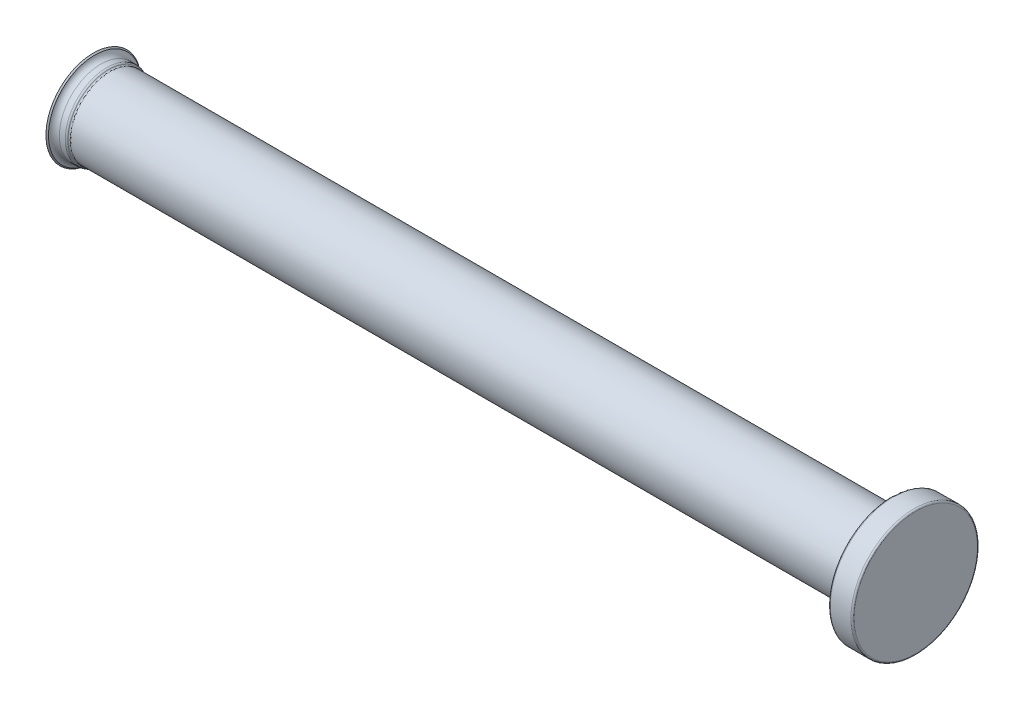
SolidWorks part; units mm, degrees
ref_plane "Ön Düzlem" through (0, 0, 0) normal (0, 0, 1) x (1, 0, 0)
ref_plane "Üst Düzlem" through (0, 0, 0) normal (0, 1, 0) x (1, 0, 0)
ref_plane "Sağ Düzlem" through (0, 0, 0) normal (1, 0, 0) x (0, 0, -1)
sketch "Çizim1" plane through (0, 0, 0) normal (0, 0, 1) x (1, 0, 0)
  line L0 (0, 0) -> (-51, 0)
  line L1 (0, 0) -> (0, 4)
  line L2 (0, 4) -> (-1.5, 4)
  line L3 (-1.5, 4) -> (-1.5, 2.5)
  line L4 (-1.5, 2.5) -> (-51, 2.5)
  line L5 (0, 0) -> (21.8777, 0) construction
  line L6 (-51, 2.5) -> (-51, 0)
  dimension "D1" = 5
  dimension "D2" = 1.5
  dimension "D3" = 8
  dimension "D4" = 49.5
revolve "Döndür1" add sketch "Çizim1" angle 360 about L5
fillet "Radyus1" radius 0.1 2 edges at (0, 0, 4) (-1.5, 0, 4)
sketch "Çizim3" plane through (-51, 0, 0) normal (-1, 0, 0) x (0, 0, 1)
  circle A1 centre (0, 0) radius 2.5
  circle A2 centre (0, 0) radius 2.5
  dimension "D1" = 0
extrude "Kes-Ekstrüzyon1" cut sketch "Çizim3" against normal blind 10 draft 80
sketch "Çizim4" plane through (0, 0, 0) normal (0, 0, 1) x (1, 0, 0)
  line L0 (-51, 2.5) -> (-51, -2.5) construction
  line L1 (-51, 2.5) -> (-51, -2.5) construction
  line L2 (-51, 2.5) -> (-51.5, 2.5) construction
  line L3 (-52.0081, 2.8924) -> (-51.887, 2.9241) construction
  line L4 (-51.5, 2.5) -> (-51.1221, 2.5)
  line L5 (-51.1252, 2.6252) -> (-51.5, 2.6252)
  line L6 (-52.0081, 2.8924) -> (-51.9716, 3)
  line L7 (-51.9716, 3) -> (-51.887, 2.9241)
  line L8 (-51.9716, 3) -> (-51.9476, 2.9082) construction
  line L9 (-1.5, 3.9) -> (-1.5, -3.9) construction
  line L10 (-51, 0) -> (-55.9233, 0) construction
  line L11 (-51, 2.5) -> (-51, 2.4026) construction
  line L15 (-50.9083, 2.0006) -> (-51, 2.4026)
  line L16 (-50.9083, 2.5) -> (-50.9083, 2.0006)
  line L17 (-1.5, 2.5) -> (-51, 2.5) construction
  line L18 (-1.5, 2.5) -> (-51, 2.5) construction
  arc A0 (-51.5, 2.5) -> (-52.0081, 2.8924) centre (-51.5, 3.0252) cw
  arc A1 (-51.1221, 2.5) -> (-51, 2.4026) centre (-51.1221, 2.3748) cw
  arc A2 (-51, 2.5) -> (-51.1252, 2.6252) centre (-51.1252, 2.5) ccw construction
  arc A3 (-51.5, 2.6252) -> (-51.887, 2.9241) centre (-51.5, 3.0252) cw
  arc A4 (-51.1252, 2.6252) -> (-51.0168, 2.5626) centre (-51.1252, 2.5) cw
  arc A5 (-51.0168, 2.5626) -> (-50.9083, 2.5) centre (-50.9083, 2.6252) ccw
  dimension "D2" = 0.4
  dimension "D3" = 0.1252
  dimension "D1" = 50
  dimension "D4" = 0.0846
  dimension "D5" = 6
  dimension "D6" = 0.4994
revolve "Döndür2" add sketch "Çizim4" angle 360 about L10
ref_axis "Eksen1" through (2.6004, 0, 0) along (-1, 0, 0)
